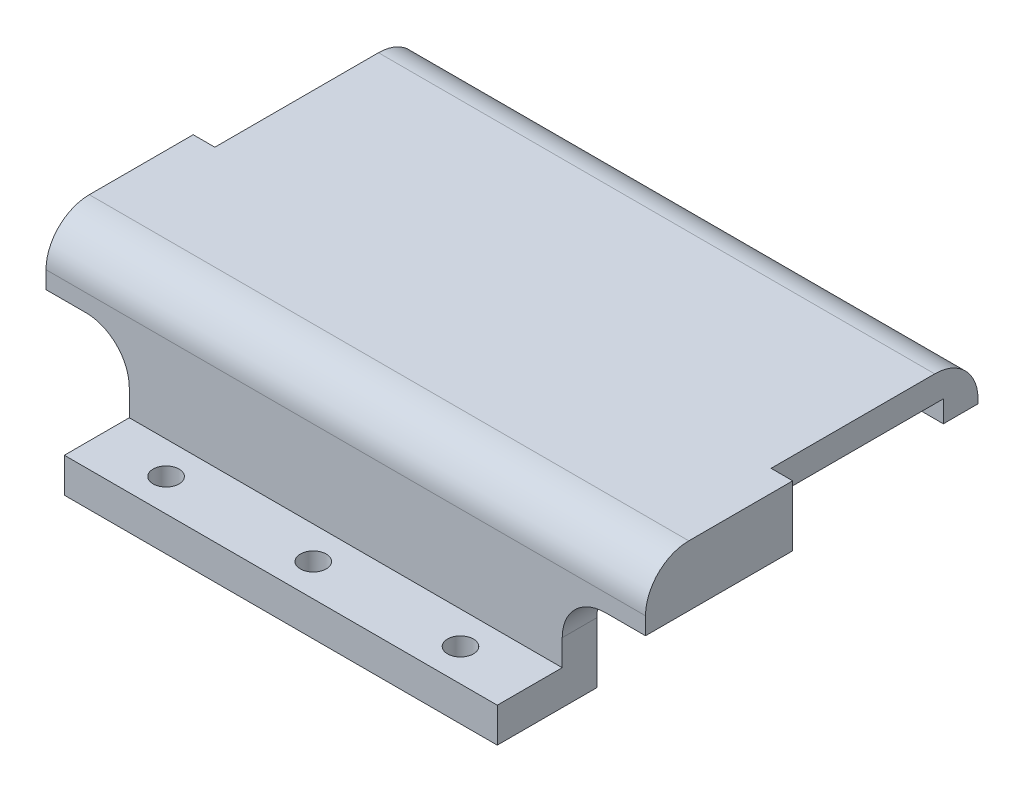
SolidWorks part; units mm, degrees
ref_plane "Front Plane" through (0, 0, 0) normal (0, 0, 1) x (1, 0, 0)
ref_plane "Top Plane" through (0, 0, 0) normal (0, 1, 0) x (1, 0, 0)
ref_plane "Right Plane" through (0, 0, 0) normal (1, 0, 0) x (0, 0, -1)
sketch "Sketch1" plane through (0, 0, 0) normal (0, 1, 0) x (1, 0, 0)
  line L1 (-40.7924, -25.9715) -> (40.7924, -25.9715)
  line L2 (-40.7924, -25.9715) -> (-40.7924, 25.9715)
  line L3 (-40.7924, 25.9715) -> (40.7924, 25.9715)
  line L4 (40.7924, -25.9715) -> (40.7924, 25.9715)
  line L5 (-40.7924, -25.9715) -> (40.7924, 25.9715) construction
  line L6 (-40.7924, 25.9715) -> (40.7924, -25.9715) construction
  point P0 (0, 0)
  dimension "D1" = 51.943
  dimension "D2" = 81.5848
extrude "Boss-Extrude1" add sketch "Sketch1" along normal blind 3.81
sketch "Sketch2" plane through (0, 0, 0) normal (0, -1, 0) x (1, 0, 0)
  line L1 (-31.75, 25.9715) -> (31.75, 25.9715)
  line L2 (-31.75, 25.9715) -> (-31.75, 20.8915)
  line L3 (-31.75, 20.8915) -> (31.75, 20.8915)
  line L4 (31.75, 25.9715) -> (31.75, 20.8915)
  line L5 (0, 25.9715) -> (0, -25.9715) construction
  line L6 (40.7924, -25.9715) -> (-40.7924, -25.9715) construction
  line L7 (-40.7924, 25.9715) -> (40.7924, 25.9715) construction
  dimension "D1" = 5.08
  dimension "D2" = 63.5
extrude "Boss-Extrude2" add sketch "Sketch2" along normal blind 20.32
sketch "Sketch3" plane through (0, 0, 0) normal (0, -1, 0) x (1, 0, 0)
  line L0 (40.7924, 25.9715) -> (40.7924, -25.9715) construction
  line L1 (-40.7924, -25.9715) -> (40.7924, -25.9715)
  line L2 (-40.7924, -25.9715) -> (-40.7924, -20.8915)
  line L3 (-40.7924, -20.8915) -> (40.7924, -20.8915)
  line L4 (40.7924, -25.9715) -> (40.7924, -20.8915)
  dimension "D1" = 5.08
extrude "Boss-Extrude3" add sketch "Sketch3" along normal blind 3.175
sketch "Sketch4" plane through (0, 0, 25.9715) normal (0, 0, 1) x (1, 0, 0)
  line L1 (-31.75, -20.32) -> (31.75, -20.32)
  line L2 (-31.75, -20.32) -> (-31.75, -15.24)
  line L3 (-31.75, -15.24) -> (31.75, -15.24)
  line L4 (31.75, -20.32) -> (31.75, -15.24)
  line L5 (-31.75, -20.32) -> (-31.75, 0) construction
  line L6 (31.75, -20.32) -> (31.75, 0) construction
  line L7 (31.75, -20.32) -> (-31.75, -20.32) construction
  dimension "D1" = 5.08
extrude "Boss-Extrude4" add sketch "Sketch4" along normal blind 9.525
sketch "Sketch6" plane through (0, 3.81, 0) normal (0, 1, 0) x (1, 0, 0)
  line L1 (-40.7924, -25.9715) -> (-43.9674, -25.9715)
  line L2 (-40.7924, -25.9715) -> (-40.7924, -4.3815)
  line L3 (-40.7924, -4.3815) -> (-43.9674, -4.3815)
  line L4 (-43.9674, -25.9715) -> (-43.9674, -4.3815)
  line L5 (40.7924, -25.9715) -> (43.9674, -25.9715)
  line L6 (40.7924, -25.9715) -> (40.7924, -4.3815)
  line L7 (40.7924, -4.3815) -> (43.9674, -4.3815)
  line L8 (43.9674, -25.9715) -> (43.9674, -4.3815)
  dimension "D1" = 3.175
  dimension "D2" = 3.175
  dimension "D3" = 21.59
extrude "Boss-Extrude5" add sketch "Sketch6" against normal blind 8.89
fillet "Fillet1" radius 6.35 1 edges at (0, 3.81, -25.9715)
sketch "Sketch7" plane through (0, 0, 25.9715) normal (0, 0, 1) x (1, 0, 0)
  line L1 (40.7924, -5.08) -> (31.75, -5.08)
  line L2 (40.7924, -5.08) -> (40.7924, 0)
  line L3 (40.7924, 0) -> (31.75, 0)
  line L4 (31.75, -5.08) -> (31.75, 0)
  line L5 (-40.7924, -5.08) -> (-31.75, -5.08)
  line L6 (-40.7924, -5.08) -> (-40.7924, 0)
  line L7 (-40.7924, 0) -> (-31.75, 0)
  line L8 (-31.75, -5.08) -> (-31.75, 0)
extrude "Boss-Extrude6" add sketch "Sketch7" against normal up to surface (5.08 mm away) up to face at (0, -10.16, 20.8915)
fillet "Fillet2" radius 6.35 2 edges at (-31.75, -5.08, 23.4315) (31.75, -5.08, 23.4315)
fillet "Fillet3" radius 6.35 1 edges at (0, 3.81, 25.9715)
sketch "Sketch8" plane through (0, 0, 0) normal (0, -1, 0) x (1, 0, 0)
  line L0 (0, 20.8915) -> (0, -20.8915) construction
  line L1 (-31.75, 20.8915) -> (31.75, 20.8915) construction
  line L2 (40.7924, -20.8915) -> (-40.7924, -20.8915) construction
  line L3 (-40.7924, 20.8915) -> (40.7924, 20.8915) construction
  line L4 (-0.635, 20.8915) -> (0.635, 20.8915)
  line L5 (-0.635, 20.8915) -> (-0.635, -20.8915)
  line L6 (-0.635, -20.8915) -> (0.635, -20.8915)
  line L7 (0.635, 20.8915) -> (0.635, -20.8915)
  line L8 (40.7924, -20.8915) -> (-40.7924, -20.8915) construction
  dimension "D1" = 1.27
extrude "Boss-Extrude7" add sketch "Sketch8" along normal up to surface (3.175 mm away) up to face at (0, -3.175, -23.4315)
hole_wizard "#6 Clearance Hole1" positions "3DSketch3" profile "Sketch9" hole size "#6" standard "ANSI Inch" end condition through all
sketch3d "3DSketch3"
  line L0 (-31.75, -15.24, 30.734) -> (31.75, -15.24, 30.734) construction
  line L1 (-31.75, -15.24, 35.4965) -> (-31.75, -15.24, 25.9715) construction
  line L2 (31.75, -15.24, 35.4965) -> (31.75, -15.24, 25.9715) construction
  point P8 (-21.59, -15.24, 30.734)
  point P10 (0, -15.24, 30.734)
  point P12 (21.59, -15.24, 30.734)
  point P16 (0, 0, 0)
  point P17 (0, 0, 0)
  point P18 (0, 0, 0)
  dimension "D2" = 10.16
  dimension "D1" = 10.16
sketch "Sketch9" plane through (21.59, -15.24, 30.734) normal (1, 0, 0) x (0, 0, 1)
  line L0 (0, 0) -> (0, 5.08)
  line L1 (0, 5.08) -> (1.8986, 5.08)
  line L2 (1.8986, 5.08) -> (1.8986, 0)
  line L5 (1.8986, 0) -> (0, 0)
  line L11 (0, -6.35) -> (0, 107.95) construction
  dimension "Thru Hole Dia." = 3.7973
  dimension "Thru Hole Depth" = 5.08
equation "\"D2@Sketch6\"=\"D1@Sketch6\""
equation "\"D2@3DSketch3\"=\"D1@3DSketch3\""
